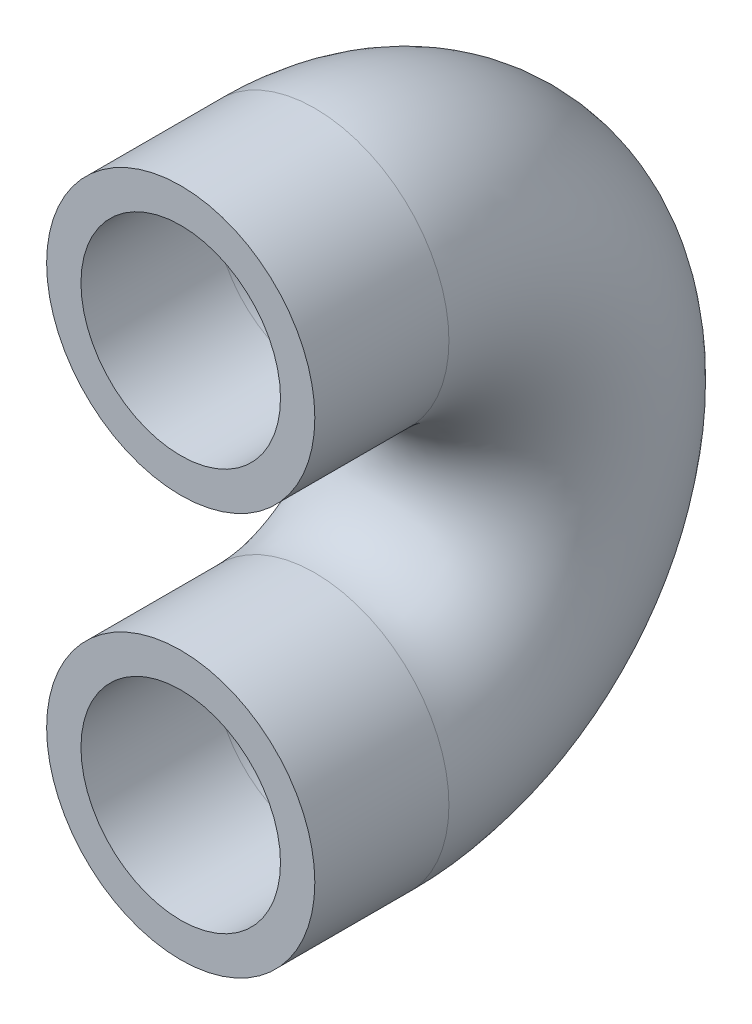
SolidWorks part; units mm, degrees
ref_plane "Front Plane" through (0, 0, 0) normal (0, 0, 1) x (1, 0, 0)
ref_plane "Top Plane" through (0, 0, 0) normal (0, 1, 0) x (1, 0, 0)
ref_plane "Right Plane" through (0, 0, 0) normal (1, 0, 0) x (0, 0, -1)
sketch "Sketch1" plane through (0, 0, 0) normal (0, 0, 1) x (1, 0, 0)
  circle A0 centre (-4.7625, 13.335) radius 2.3622
  circle A1 centre (-4.7625, 13.335) radius 3.175
  circle A2 centre (-4.7625, 3.81) radius 2.3622
  circle A3 centre (-4.7625, 3.81) radius 3.175
  dimension "D1" = 4.7244
  dimension "D2" = 6.35
  dimension "D3" = 9.525
  dimension "D4" = 6.35
  dimension "D5" = 4.7244
extrude "Boss-Extrude1" add sketch "Sketch1" along normal blind 3.175
sketch "Sketch2" plane through (0, 0, 0) normal (0, 0, -1) x (-1, 0, 0)
  line L0 (4.8883, 8.5725) -> (-3.3832, 8.5725) construction
  point P2 (4.7625, 3.81)
  point P3 (4.7625, 13.335)
revolve "Revolve1" add sketch "Sketch2" angle 180 about L0 region at (-1.6773, 13.335, 0) reverse direction yes
